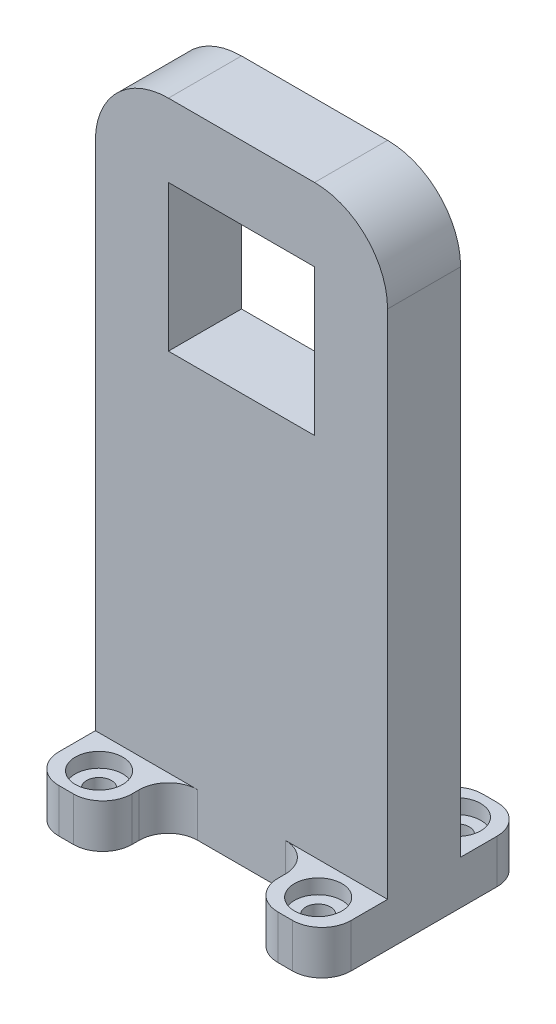
SolidWorks part; units mm, degrees
ref_plane "Plan de face" through (0, 0, 0) normal (0, 0, 1) x (1, 0, 0)
ref_plane "Plan de dessus" through (0, 0, 0) normal (0, 1, 0) x (1, 0, 0)
ref_plane "Plan de droite" through (0, 0, 0) normal (1, 0, 0) x (0, 0, -1)
sketch "Esquisse1" plane through (0, 0, 0) normal (0, 0, 1) x (1, 0, 0)
  line L0 (0, 0) -> (40, 0)
  line L1 (0, 0) -> (40, 0) construction
  line L2 (0, 0) -> (0, 86) construction
  line L3 (0, 86) -> (40, 86) construction
  line L4 (40, 0) -> (40, 86) construction
  line L5 (40, 0) -> (40, 86)
  line L6 (40, 86) -> (0, 86)
  line L7 (0, 86) -> (0, 0)
  line L9 (10, 76) -> (30, 76)
  line L10 (10, 76) -> (10, 56)
  line L11 (10, 56) -> (30, 56)
  line L12 (30, 76) -> (30, 56)
  dimension "D1" = 40
  dimension "D2" = 86
  dimension "D3" = 10
  dimension "D4" = 10
  dimension "D5" = 10
  dimension "D6" = 56
extrude "Boss.-Extru.1" add sketch "Esquisse1" along normal blind 10
sketch "Esquisse3" plane through (0, 0, 10) normal (0, 0, 1) x (1, 0, 0)
  line L0 (30, 0) -> (40, 0)
  line L3 (0, 6) -> (10, 6)
  line L4 (0, 86) -> (0, 0)
  line L5 (0, 0) -> (40, 0)
  line L6 (40, 0) -> (40, 86)
  line L7 (40, 86) -> (0, 86)
  line L8 (0, 6) -> (0, 0)
  line L9 (0, 0) -> (10, 0)
  line L12 (10, 0) -> (10, 6)
  line L14 (40, 0) -> (40, 6)
  line L15 (40, 6) -> (30, 6)
  line L16 (30, 0) -> (30, 6)
  line L17 (0, 0) -> (40, 0) construction
  dimension "D4" = 10
  dimension "D2" = 10
  dimension "D3" = 6
  dimension "D5" = 6
extrude "Boss.-Extru.2" add sketch "Esquisse3" along normal blind 9
sketch "Esquisse4" plane through (0, 6, 0) normal (0, 1, 0) x (1, 0, 0)
  line L0 (0, -19) -> (0, -10) construction
  line L1 (10, -10) -> (0, -10) construction
  line L2 (40, -19) -> (40, -10) construction
  line L3 (40, -10) -> (0, -10) construction
  circle A0 centre (5, -14.5) radius 1.5
  circle A1 centre (35, -14.5) radius 1.5
  dimension "D3" = 3
  dimension "D4" = 3
  dimension "D1" = 5
  dimension "D2" = 4.5
  dimension "D5" = 5
  dimension "D6" = 4.5
hole_wizard "Chambrage pour tête cylindrique fendue M31" positions "Esquisse5" profile "Esquisse6" counterbore size "M3" standard "ISO" end condition through all
sketch "Esquisse5" plane through (0, 6, 0) normal (0, 1, 0) x (1, 0, 0)
  point P0 (5, -14.5)
  point P3 (35, -14.5)
sketch "Esquisse6" plane through (5, 6, 14.5) normal (1, 0, 0) x (0, 0, 1)
  line L0 (0, 0) -> (0, 6)
  line L1 (0, 6) -> (1.7, 6)
  line L3 (1.7, 6) -> (1.7, 2)
  line L4 (1.7, 2) -> (3.25, 2)
  line L5 (3.25, 2) -> (3.25, 0)
  line L7 (3.25, 0) -> (0, 0)
  line L11 (0, -6.35) -> (0, 107.95) construction
  dimension "Diamètre du perçage jusqu'au prochain" = 3.4
  dimension "Profondeur du perçage jusqu'au prochain" = 6
  dimension "Diamètre du chambrage" = 6.5
  dimension "Profondeur du chambrage" = 2
ref_plane "Plan1" through (0, 0, 5) normal (0, 0, 1) x (1, 0, 0)
mirror "Symétrie1" about plane through (0, 0, 5) normal (0, 0, 1) of "Chambrage pour tête cylindrique fendue M31", "Boss.-Extru.2"
fillet "Congé1" radius 4 12 edges at (40, 3, 19) (30, 3, 19) (0, 3, 19) (10, 3, 19) (30, 3, 10) (10, 3, 10) (0, 3, -9) (10, 3, -9) (10, 3, 0) (30, 3, 0) (30, 3, -9) (40, 3, -9)
fillet "Congé2" radius 10 2 edges at (0, 86, 5) (40, 86, 5)
equation "\"largeur_cremail\"= 20"
equation "\"hauteur_cremail\"= 20"
equation "\"epaiss_cadre\"= 10"
equation "\"hauteur_basecremail_sol\"= 122 - 76"
equation "\"D1@Esquisse1\"=\"largeur_cremail\"+\"epaiss_cadre\"*2"
equation "\"D2@Esquisse1\"=\"hauteur_basecremail_sol\"+\"hauteur_cremail\"+\"epaiss_cadre\"*2"
equation "\"D3@Esquisse1\"=\"epaiss_cadre\""
equation "\"D4@Esquisse1\"=\"epaiss_cadre\""
equation "\"D5@Esquisse1\"=\"epaiss_cadre\""
equation "\"D6@Esquisse1\"=\"hauteur_basecremail_sol\"+\"epaiss_cadre\""
equation "\"D1@Boss.-Extru.1\"=\"epaiss_cadre\""
equation "\"D2@Esquisse3\"=\"epaiss_cadre\""
equation "\"D4@Esquisse3\"=\"epaiss_cadre\""
equation "\"D5@Esquisse3\"=\"D3@Esquisse3\""
equation "\"D1@Esquisse4\"=\"epaiss_cadre\"/2"
equation "\"D5@Esquisse4\"=\"epaiss_cadre\"/2"
equation "\"D6@Esquisse4\"=4.5"
